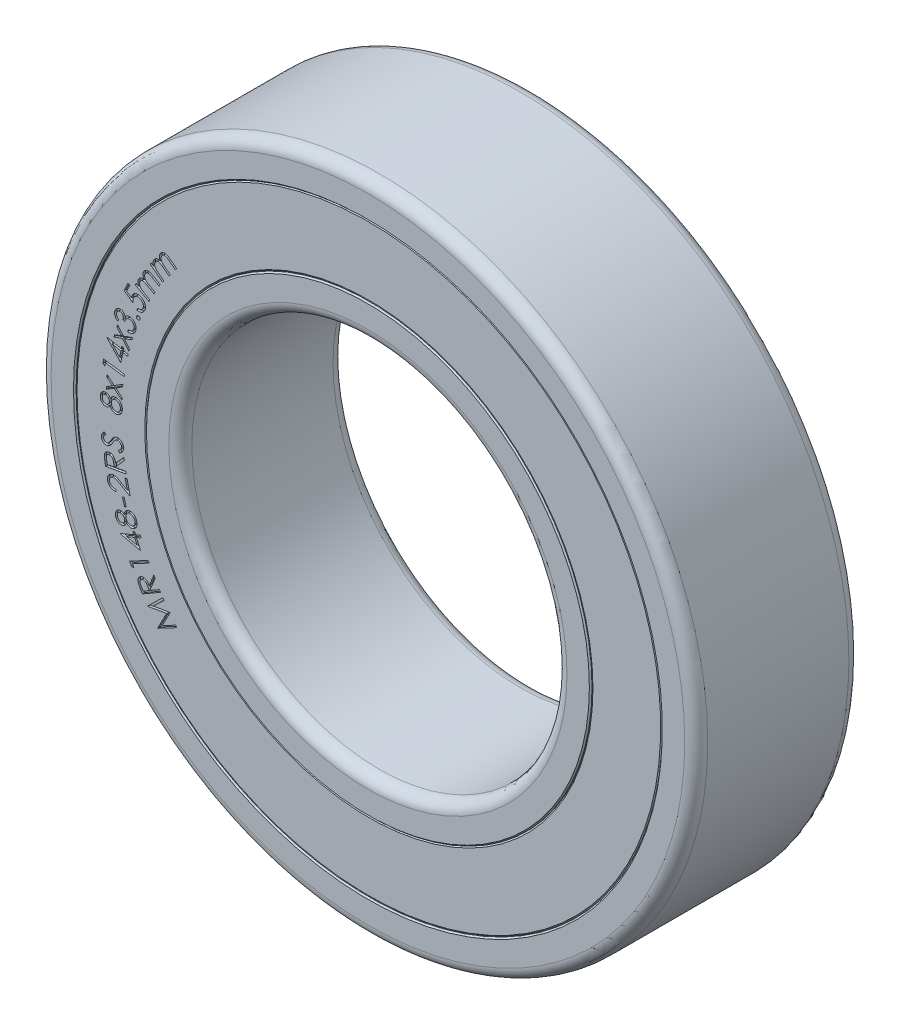
SolidWorks part; units mm, degrees
material "AISI 316 Annealed Stainless Steel Bar (SS)"
ref_plane "Front" through (0, 0, 0) normal (0, 0, 1) x (1, 0, 0)
ref_plane "Top" through (0, 0, 0) normal (0, 1, 0) x (1, 0, 0)
ref_plane "Right" through (0, 0, 0) normal (1, 0, 0) x (0, 0, -1)
sketch "LAYOUT R" plane through (0, 0, 0) normal (1, 0, 0) x (0, 0, -1)
  line L0 (-1.75, 4) -> (1.75, 4)
  line L1 (1.75, -7) -> (-1.75, -7) construction
  line L2 (1.75, -7) -> (1.75, 7) construction
  line L3 (1.75, 7) -> (-1.75, 7)
  line L4 (-1.75, -7) -> (-1.75, 7) construction
  line L5 (1.75, -7) -> (-1.75, 7) construction
  line L6 (1.75, 7) -> (-1.75, -7) construction
  line L7 (-1.75, 4.75) -> (1.75, 4.75)
  line L8 (-1.75, 6.25) -> (1.75, 6.25)
  line L11 (-17.5, 0) -> (17.5, 0) construction
  line L12 (-1.75, 7) -> (-1.75, 6.25)
  line L13 (1.75, 7) -> (1.75, 6.25)
  line L14 (-1.75, 6.25) -> (-1.75, 4.75)
  line L15 (1.75, 6.25) -> (1.75, 4.75)
  line L16 (-1.75, 4.75) -> (-1.75, 4)
  line L17 (1.75, 4.75) -> (1.75, 4)
  line L18 (-1.73, 6.25) -> (-1.73, 4.75)
  line L19 (1.73, 6.25) -> (1.73, 4.75)
  point P0 (0, 0)
  point P15 (0, 0)
  dimension "D1" = 3.5
  dimension "D2" = 14
  dimension "D3" = 4
  dimension "D6" = 0.02
  dimension "D7" = 0.02
  dimension "D4" = 4.75
  dimension "D5" = 6.25
sketch "Sketch R, INNER BODY" plane through (0, 0, 0) normal (1, 0, 0) x (0, 0, -1)
  line L0 (-1.75, 4) -> (1.75, 4) construction
  line L2 (-1.75, 4.75) -> (1.75, 4.75) construction
  line L4 (-1.75, 4) -> (1.75, 4)
  line L6 (-1.75, 4.75) -> (1.75, 4.75)
  line L8 (1.75, 4.75) -> (1.75, 4) construction
  line L9 (-1.75, 4.75) -> (-1.75, 4) construction
  line L10 (1.75, 4.75) -> (1.75, 4)
  line L11 (-1.75, 4.75) -> (-1.75, 4)
  line L12 (-17.5, 0) -> (17.5, 0) construction
  line L13 (-17.5, 0) -> (17.5, 0) construction
sketch "Sketch R, OUTER BODY" plane through (0, 0, 0) normal (1, 0, 0) x (0, 0, -1)
  line L2 (-1.75, 6.25) -> (1.75, 6.25) construction
  line L3 (1.75, 7) -> (-1.75, 7) construction
  line L6 (-1.75, 6.25) -> (1.75, 6.25)
  line L7 (1.75, 7) -> (-1.75, 7)
  line L8 (-17.5, 0) -> (17.5, 0) construction
  line L9 (-17.5, 0) -> (17.5, 0) construction
  line L10 (1.75, 7) -> (1.75, 6.25) construction
  line L11 (-1.75, 7) -> (-1.75, 6.25) construction
  line L12 (1.75, 7) -> (1.75, 6.25)
  line L13 (-1.75, 7) -> (-1.75, 6.25)
sketch "Sketch R, SEAL FACES" plane through (0, 0, 0) normal (1, 0, 0) x (0, 0, -1)
  line L0 (-17.5, 0) -> (17.5, 0) construction
  line L1 (-17.5, 0) -> (17.5, 0) construction
  line L3 (-1.75, 4.75) -> (1.75, 4.75) construction
  line L5 (-1.75, 6.25) -> (1.75, 6.25) construction
  line L7 (-1.73, 4.75) -> (1.73, 4.75)
  line L9 (-1.73, 6.25) -> (1.73, 6.25)
  line L10 (1.73, 6.25) -> (1.73, 4.75) construction
  line L11 (-1.73, 6.25) -> (-1.73, 4.75) construction
  line L12 (1.73, 6.25) -> (1.73, 4.75)
  line L13 (-1.73, 6.25) -> (-1.73, 4.75)
revolve "Revolve INNER BODY" add sketch "Sketch R, INNER BODY" angle 360 about L13
fillet "Fillet INNER BODY" radius 0.245 2 edges at (4, 0, 1.75) (4, 0, -1.75)
chamfer "Chamfer INNER BODY" distance 0.028 angle 45 2 edges at (4.75, 0, -1.75) (4.75, 0, 1.75)
revolve "Revolve OUTER BODY" add sketch "Sketch R, OUTER BODY" angle 360 about L9
fillet "Fillet OUTER BODY" radius 0.245 2 edges at (7, 0, -1.75) (7, 0, 1.75)
chamfer "Chamfer OUTER BODY" distance 0.028 angle 45 2 edges at (6.25, 0, 1.75) (6.25, 0, -1.75)
revolve "Revolve SEALS" add sketch "Sketch R, SEAL FACES" angle 360 about L1
chamfer "Chamfer SEALS" distance 0.028 angle 45 4 edges at (4.75, 0, -1.73) (6.25, 0, -1.73) (6.25, 0, 1.73) (4.75, 0, 1.73)
sketch "Sketch TEXT RADIUS 1 — MANUALLY ASSIGN TEXT AND FONT SIZE (FROM EQUATIONS)" plane through (0, 0, 1.73) normal (0, 0, 1) x (1, 0, 0)
  circle A0 centre (0, 0) radius 5.275 construction
  text T0 "MR148-2RS  8x14x3.5mm" font "Century Gothic" height 0.45
  dimension "D1" = 10.55
extrude "Cut-Extrude SEAL LABEL 1" cut sketch "Sketch TEXT RADIUS 1 — MANUALLY ASSIGN TEXT AND FONT SIZE (FROM EQUATIONS)" against normal blind 0.05
sketch "Sketch TEXT RADIUS 2 — MANUALLY ASSIGN TEXT AND FONT SIZE (FROM EQUATIONS)" plane through (0, 0, -1.73) normal (0, 0, -1) x (-1, 0, 0)
  circle A0 centre (0, 0) radius 5.275 construction
  text T0 "MR148-2RS  8x14x3.5mm" font "Century Gothic" height 0.45
  dimension "D1" = 10.55
extrude "Cut-Extrude SEAL LABEL 2" cut sketch "Sketch TEXT RADIUS 2 — MANUALLY ASSIGN TEXT AND FONT SIZE (FROM EQUATIONS)" against normal blind 0.05
equation "\"_i__BORE\"= 8"
equation "\"_i__OUTSIDE_DIAMETER\"= 14"
equation "\"_i__WIDTH\"= 3.5"
equation "\"_i_optional__TEXT_RADIUS_ADJUSTMENT\"= 0"
equation "\"_output__FONT_SIZE_mm\"= \"BODY_SPAN__SEAL__OF_RADIUS\" * \"param__FONT_SIZE_RATIO\"'MANUALLY ASSIGN TO FONT"
equation "\"BODY__HALF_WIDTH\"= \"_i__WIDTH\" / 2"
equation "\"BODY_SPAN___OF_DIAMETER\"= \"_i__OUTSIDE_DIAMETER\" - \"_i__BORE\""
equation "\"BODY_SPAN___OF_RADIUS\"= \"BODY_SPAN___OF_DIAMETER\" / 2"
equation "\"BODY_SPAN__BORE_AND_OD__OF RADIUS\"= ( \"BODY_SPAN___OF_RADIUS\" - \"BODY_SPAN__SEAL__OF_RADIUS\" ) / 2"
equation "\"BODY_SPAN__SEAL__OF_RADIUS\"= \"BODY_SPAN___OF_RADIUS\" * \"param__SEAL_PANEL_SPAN__RATIO_OF_BODY_RADIAN\""
equation "\"BORE__RADIUS\"= \"_i__BORE\" / 2"
equation "\"CORNER_RADII\"= \"_i__WIDTH\" * \"param__CORNER_RADII__ISO_MAX_RATIO_TO_WIDTH\""
equation "\"param__CORNER_RADII__ISO_MAX_RATIO_TO_WIDTH\"= 0.07'WHERE WIDTH IS LESS THAN DIAMETER"
equation "\"param__FONT_SIZE_RATIO\"= 0.3"
equation "\"param__SEAL_FACE_INSET__RATIO_OF_WIDTH\"= .01"
equation "\"param__SEAL_PANEL_SPAN__RATIO_OF_BODY_RADIAN\"= 0.5"
equation "\"param__SIDE_CHAMFERS__RATIO_TO_OD\"= 1 / 500"
equation "\"RING_INNER__OUTSIDE_RADIUS\"= \"BORE__RADIUS\" + \"BODY_SPAN__BORE_AND_OD__OF RADIUS\""
equation "\"RING_OUTER__OUTSIDE_RADIUS\"= ( \"_i__OUTSIDE_DIAMETER\" / 2 ) - \"BODY_SPAN__BORE_AND_OD__OF RADIUS\""
equation "\"SEAL_FACE_INSET\"= \"_i__WIDTH\" * \"param__SEAL_FACE_INSET__RATIO_OF_WIDTH\""
equation "\"SIDE_FACE_AND_SEAL_CHAMFERS\"= \"_i__OUTSIDE_DIAMETER\" * \"param__SIDE_CHAMFERS__RATIO_TO_OD\""
equation "\"TEXT_RADIUS\"= \"_i__BORE\" + ( \"BODY_SPAN___OF_DIAMETER\" / 2 ) - \"_output__FONT_SIZE_mm\" + \"_i_optional__TEXT_RADIUS_ADJUSTMENT\""
equation "\"D1@Chamfer INNER BODY\"=\"SIDE_FACE_AND_SEAL_CHAMFERS\""
equation "\"D1@Chamfer OUTER BODY\"=\"SIDE_FACE_AND_SEAL_CHAMFERS\""
equation "\"D1@Chamfer SEALS\"=\"SIDE_FACE_AND_SEAL_CHAMFERS\""
equation "\"D1@Fillet INNER BODY\"=\"CORNER_RADII\""
equation "\"D1@Fillet OUTER BODY\"=\"CORNER_RADII\""
equation "\"D1@LAYOUT R\"=\"_i__WIDTH\""
equation "\"D1@Sketch TEXT RADIUS 1 — MANUALLY ASSIGN TEXT AND FONT SIZE (FROM EQUATIONS)\" = \"TEXT_RADIUS\""
equation "\"D1@Sketch TEXT RADIUS 2 — MANUALLY ASSIGN TEXT AND FONT SIZE (FROM EQUATIONS)\" = \"TEXT_RADIUS\""
equation "\"D2@LAYOUT R\"=\"_i__OUTSIDE_DIAMETER\""
equation "\"D3@LAYOUT R\"=\"BORE__RADIUS\""
equation "\"D4@LAYOUT R\"=\"RING_INNER__OUTSIDE_RADIUS\""
equation "\"D5@LAYOUT R\"=\"RING_OUTER__OUTSIDE_RADIUS\""
